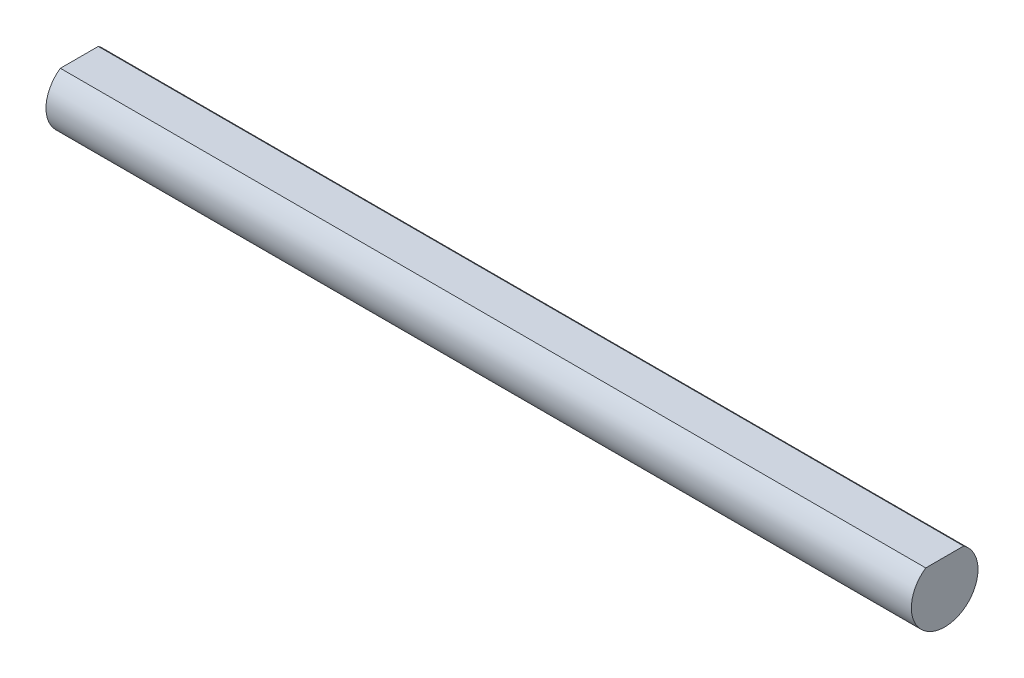
SolidWorks part; units mm, degrees
ref_plane "Front Plane" through (0, 0, 0) normal (0, 0, 1) x (1, 0, 0)
ref_plane "Top Plane" through (0, 0, 0) normal (0, 1, 0) x (1, 0, 0)
ref_plane "Right Plane" through (0, 0, 0) normal (1, 0, 0) x (0, 0, -1)
sketch "Sketch1" plane through (0, 0, 0) normal (1, 0, 0) x (0, 0, -1)
  line L1 (1.0951, 1.5832) -> (-1.0951, 1.5832)
  arc A0 (-1.0951, 1.5832) -> (1.0951, 1.5832) centre (0, 0) ccw
  dimension "D1" = 3.85
extrude "Boss-Extrude1" add sketch "Sketch1" along normal mid plane 50
